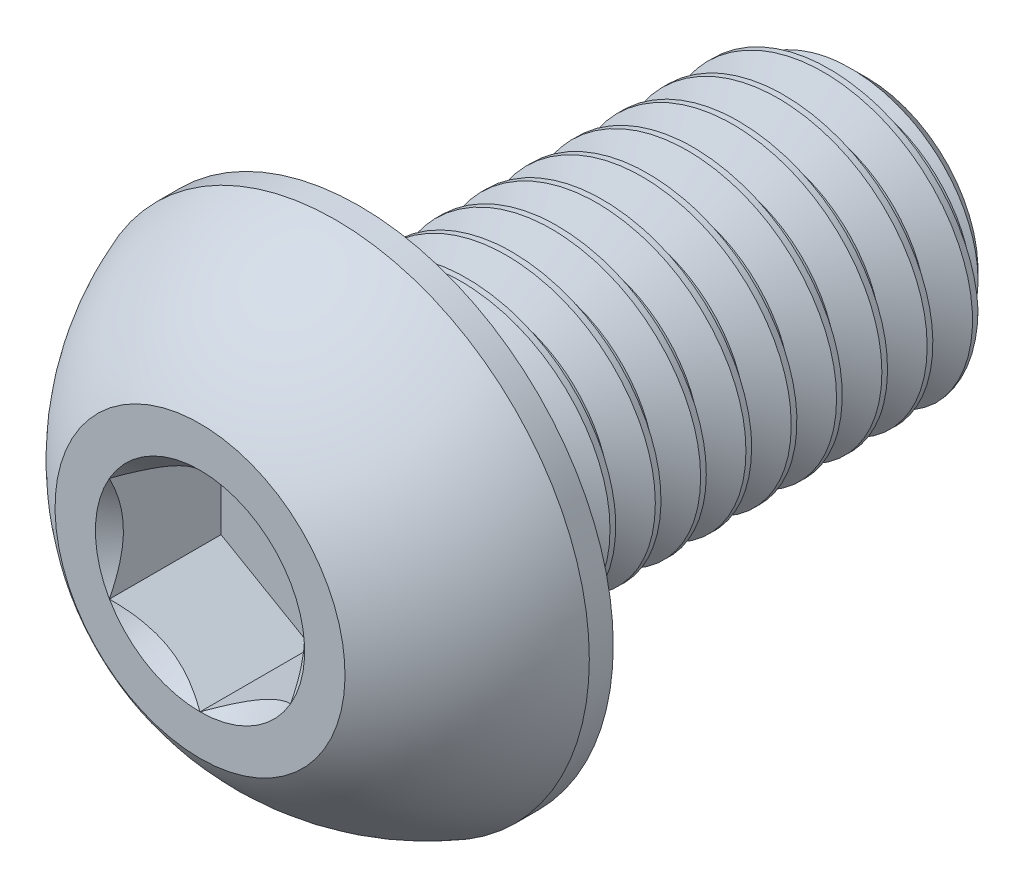
SolidWorks part; units mm, degrees
ref_plane "Front" through (0, 0, 0) normal (0, 0, 1) x (1, 0, 0)
ref_plane "Top" through (0, 0, 0) normal (0, 1, 0) x (1, 0, 0)
ref_plane "Right" through (0, 0, 0) normal (1, 0, 0) x (0, 0, -1)
sketch "Sketch1" plane through (0, 0, 0) normal (1, 0, 0) x (0, 0, -1)
  line L2 (4.4, 4) -> (18.4, 4)
  line L3 (18.4, 4) -> (18.4, 0)
  line L4 (18.4, 0) -> (4.4, 0)
  line L6 (3.74, 7) -> (4.4, 7) construction
  line L7 (18.4, 4) -> (18.4, -4) construction
  line L8 (0, 0) -> (4.4, 0) construction
  line L9 (4.4, 7) -> (4.4, -7) construction
  line L11 (4.4, 4) -> (4.4, 0)
  line L13 (0, 2.5) -> (0, -2.5) construction
  line L14 (0, 2.5) -> (0, 4) construction
  arc A3 (0, 4) -> (3.74, 7) centre (6.2818, 0) cw construction
  dimension "D1" = 0.66
  dimension "Head Ht" = 4.4
  dimension "Head Dia" = 14
  dimension "Dia" = 8
  dimension "Lg" = 14
  dimension "Hex" = 5
revolve "Revolve1" add sketch "Sketch1" angle 360 mid plane about L4
sketch "Sketch3" plane through (0, 0, -18.4) normal (0, 0, -1) x (-1, 0, 0)
  circle A0 centre (0, 0) radius 4
curve "Helix/Spiral1" pitch 1.25 height 15.25 radius 4 centre (0, 0, -18.4) axis (0, 0, 1) start towards (0, 1, 0)
sketch "Sketch2" plane through (0, 0, 0) normal (1, 0, 0) x (0, 0, -1)
  line L0 (18.4, 4) -> (19.4938, 4)
  line L1 (19.4938, 4) -> (19.025, 3.1881)
  line L2 (19.025, 3.1881) -> (18.8688, 3.1881)
  line L3 (18.8688, 3.1881) -> (18.4, 4)
  line L4 (18.6344, 3.5941) -> (19.2594, 3.5941) construction
  dimension "D1" = 60
  dimension "D2" = 0.1562
  dimension "D3" = 0.625
chamfer "Chamfer1" distance 0.9375 angle 45 1 edges at (0, 4, -18.4)
sweep "Cut-Sweep1" cut profiles "Sketch2" path "Helix/Spiral1"
sketch "Sketch7" plane through (0, 0, 0) normal (1, 0, 0) x (0, 0, -1)
  line L6 (3.74, 7) -> (4.4, 7) construction
  line L8 (0, 0) -> (4.4, 0) construction
  line L11 (4.4, 7) -> (4.4, -7) construction
  line L12 (3.74, 7) -> (4.4, 7)
  line L13 (0, 0) -> (4.4, 0)
  line L14 (0, 2.5) -> (0, -2.5) construction
  line L15 (4.4, 7) -> (4.4, 0)
  line L16 (0, 4) -> (0, 0)
  arc A2 (3.74, 7) -> (0, 4) centre (6.2818, 0) ccw construction
  arc A3 (3.74, 7) -> (0, 4) centre (6.2818, 0) ccw
revolve "Revolve2" add sketch "Sketch7" angle 360 mid plane about L13
sketch "Sketch5" plane through (0, 0, 0) normal (0, 0, 1) x (1, 0, 0)
  line L1 (2.5, -1.4434) -> (2.5, 1.4434)
  line L2 (2.5, 1.4434) -> (0, 2.8868)
  line L3 (0, 2.8868) -> (-2.5, 1.4434)
  line L4 (-2.5, 1.4434) -> (-2.5, -1.4434)
  line L5 (-2.5, -1.4434) -> (0, -2.8868)
  line L6 (0, -2.8868) -> (2.5, -1.4434)
  circle A0 centre (0, 0) radius 2.5 construction
extrude "Cut-Extrude2" cut sketch "Sketch5" against normal blind 3.08
sketch "Sketch6" plane through (0, 0, 0) normal (0, 0, 1) x (1, 0, 0)
  circle A0 centre (0, 0) radius 2.8868
extrude "Cut-Extrude3" cut sketch "Sketch6" against normal blind 3.08 draft 45
sketch "Sketch9" [suppressed] plane through (0, 0, -4.4) normal (0, 0, 1) x (1, 0, 0)
  circle A2 centre (0, 0) radius 4
extrude "Boss-Extrude2" [suppressed] add sketch "Sketch9" against normal offset from surface (17 mm away) 22 up to face at (0, 3.0625, -18.4)
sketch "Sketch10" plane through (0, 0, 0) normal (1, 0, 0) x (0, 0, -1)
  line L0 (18.4, 4) -> (18.4, -4) construction
  point P0 (16.525, -4)
  dimension "D1" = 1.875
equation "\"D3@Helix/Spiral1\" = \"Lg@Sketch1\" + \"D4@Helix/Spiral1\""
equation "\"D2@Sketch2\" = \"D4@Helix/Spiral1\" * .125"
equation "\"D3@Sketch2\" = \"D4@Helix/Spiral1\" * .5"
equation "\"D1@Chamfer1\" = \"D4@Helix/Spiral1\" * .75"
equation "\"D1@Cut-Extrude2\" = \"Head Ht@Sketch1\" * .7"
equation "\"D1@Sketch1\" = \"Head Ht@Sketch1\" * .15"
equation "\"D1@Sketch10\" = \"D4@Helix/Spiral1\" * 1.5"
equation "\"D1@Cut-Extrude3\" = \"D1@Cut-Extrude2\""
